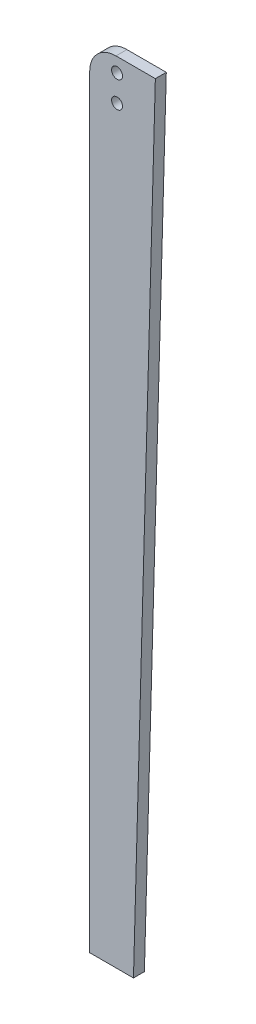
SolidWorks part; units mm, degrees
ref_plane "Front Plane" through (0, 0, 0) normal (0, 0, 1) x (1, 0, 0)
ref_plane "Top Plane" through (0, 0, 0) normal (0, 1, 0) x (1, 0, 0)
ref_plane "Right Plane" through (0, 0, 0) normal (1, 0, 0) x (0, 0, -1)
sketch "Sketch1" plane through (0, 0, 0) normal (0, 0, 1) x (1, 0, 0)
  line L0 (0, 0) -> (0, -7.62) construction
  line L1 (-0.3175, 4.1275) -> (11.1125, 4.1275)
  line L2 (-7.9375, -3.4925) -> (-7.9375, -225.1075)
  line L3 (-7.9375, -225.1075) -> (4.7625, -225.1075)
  line L4 (11.1125, 4.1275) -> (4.7625, -225.1075)
  circle A0 centre (0, 0) radius 1.5875
  circle A1 centre (0, -7.62) radius 1.5875
  arc A2 (-0.3175, 4.1275) -> (-7.9375, -3.4925) centre (-0.3175, -3.4925) ccw
  point P11 (-7.9375, 4.1275)
  dimension "D3" = 3.175
  dimension "D7" = 7.62
  dimension "D1" = 229.235
  dimension "D2" = 19.05
  dimension "D4" = 7.9375
  dimension "D5" = 4.1275
  dimension "D6" = 7.62
  dimension "D8" = 12.7
extrude "Boss-Extrude1" add sketch "Sketch1" along normal blind 3.175
